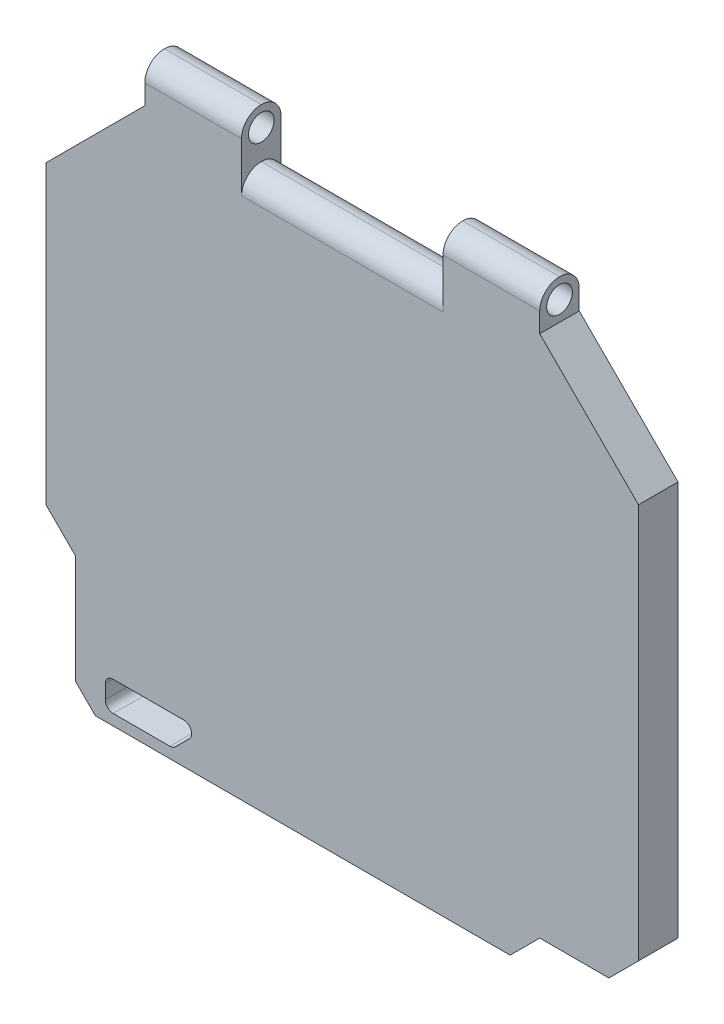
SolidWorks part; units mm, degrees
ref_plane "前视基准面" through (0, 0, 0) normal (0, 0, 1) x (1, 0, 0)
ref_plane "上视基准面" through (0, 0, 0) normal (0, 1, 0) x (1, 0, 0)
ref_plane "右视基准面" through (0, 0, 0) normal (1, 0, 0) x (0, 0, -1)
sketch "草图1" plane through (0, 0, 0) normal (0, 0, 1) x (1, 0, 0)
  line L1 (-15, -15) -> (15, -15)
  line L2 (-15, -15) -> (-15, 15)
  line L3 (-15, 15) -> (15, 15)
  line L4 (15, -15) -> (15, 15)
  line L5 (-15, -15) -> (15, 15) construction
  line L6 (-15, 15) -> (15, -15) construction
  point P0 (0, 0)
  dimension "D1" = 30
  dimension "D2" = 30
extrude "凸台-拉伸1" add sketch "草图1" along normal blind 2
sketch "草图2" plane through (0, 15, 0) normal (0, 1, 0) x (1, 0, 0)
  line L0 (15, 0) -> (-15, 0) construction
  line L1 (-5.1, -2) -> (5.1, -2)
  line L2 (-5.1, -2) -> (-5.1, 0)
  line L3 (-5.1, 0) -> (5.1, 0)
  line L4 (5.1, -2) -> (5.1, 0)
  line L5 (-5.1, -2) -> (5.1, 0) construction
  line L6 (-5.1, 0) -> (5.1, -2) construction
  line L7 (15, -2) -> (-15, -2) construction
  point P0 (0, -1)
  point P7 (0, -2)
  dimension "D1" = 10.2
extrude "切除-拉伸1" cut sketch "草图2" against normal blind 2.5
sketch "草图4" plane through (0, 0, 0) normal (0, 0, -1) x (-1, 0, 0)
  line L0 (-10, -13.5) -> (-8.5, -15)
  line L1 (-15, -15) -> (-10, -15)
  line L2 (-15, -15) -> (-15, -13.5)
  line L3 (-15, -13.5) -> (-10, -13.5)
  line L5 (15, -15) -> (-15, -15) construction
  line L6 (-8.5, -15) -> (-10, -15)
  dimension "D1" = 5
  dimension "D2" = 1.5
  dimension "D3" = 1.5
  dimension "D4" = 45
extrude "切除-拉伸3" cut sketch "草图4" against normal blind 43
chamfer "倒角1" distance 1.5 angle 45 1 edges at (15, -13.5, 1)
sketch "草图5" plane through (0, 0, 0) normal (0, 0, -1) x (-1, 0, 0)
  line L0 (-15, -12) -> (-5, -12)
  line L1 (-5, -12) -> (-2, -15)
  line L2 (-8.5, -15) -> (-2, -15)
  line L3 (15, -15) -> (-8.5, -15) construction
  line L14 (-15, 15) -> (-15, -12)
  line L15 (-15, -12) -> (-13.5, -13.5)
  line L16 (-13.5, -13.5) -> (-10, -13.5)
  line L17 (-10, -13.5) -> (-8.5, -15)
  line L18 (-8.5, -15) -> (15, -15)
  line L20 (15, -15) -> (15, 15)
  line L22 (15, 15) -> (5.1, 15)
  line L23 (5.1, 15) -> (5.1, 12.5)
  line L24 (5.1, 12.5) -> (-5.1, 12.5)
  line L25 (-5.1, 12.5) -> (-5.1, 15)
  line L26 (-5.1, 15) -> (-15, 15)
  line L29 (-15, -12) -> (-13.5, -13.5)
  line L30 (-13.5, -13.5) -> (-10, -13.5)
  line L31 (-10, -13.5) -> (-8.5, -15)
  dimension "D2" = 45
  dimension "D3" = 10
  dimension "D1" = 0
extrude "切除-拉伸4" cut sketch "草图5" against normal blind 0.5
fillet "圆角1" radius 1 6 edges at (10.05, 15, 2) (10.05, 15, 0) (-10.05, 15, 2) (-10.05, 15, 0) (0, 12.5, 2) (0, 12.5, 0)
sketch "草图3" plane through (-5.1, 0, 0) normal (1, 0, 0) x (0, 0, -1)
  circle A0 centre (-1, 14) radius 0.65
  arc A1 (0, 14) -> (-1, 15) centre (-1, 14) ccw construction
  dimension "D1" = 1.3
extrude "切除-拉伸2" cut sketch "草图3" against normal blind 43 and the other way blind 43
sketch "草图9" plane through (0, 0, 0) normal (0, 0, -1) x (-1, 0, 0)
  line L0 (-2.2933, -12.5854) -> (-0.408, -14.4707)
  line L1 (-0.3373, -14.5) -> (1.5006, -14.5)
  line L2 (1.536, -14.4146) -> (-0.3494, -12.5293)
  line L3 (-0.4201, -12.5) -> (-2.258, -12.5)
  line L4 (15, -15) -> (-2, -15) construction
  line L5 (-5, -12) -> (-15, -12) construction
  line L6 (-2, -15) -> (-5, -12) construction
  line L7 (2.5799, -12.5) -> (0.742, -12.5)
  line L8 (0.7067, -12.5854) -> (2.592, -14.4707)
  line L9 (2.6627, -14.5) -> (4.5006, -14.5)
  line L10 (4.536, -14.4146) -> (2.6506, -12.5293)
  line L11 (5.5799, -12.5) -> (3.742, -12.5)
  line L12 (3.7067, -12.5854) -> (5.592, -14.4707)
  line L13 (5.6627, -14.5) -> (7.5006, -14.5)
  line L14 (7.536, -14.4146) -> (5.6506, -12.5293)
  arc A0 (1.5006, -14.5) -> (1.536, -14.4146) centre (1.5006, -14.45) ccw
  arc A1 (-2.2933, -12.5854) -> (-2.258, -12.5) centre (-2.258, -12.55) cw
  arc A2 (-0.3373, -14.5) -> (-0.408, -14.4707) centre (-0.3373, -14.4) cw
  arc A3 (-0.3494, -12.5293) -> (-0.4201, -12.5) centre (-0.4201, -12.6) ccw
  arc A4 (2.6506, -12.5293) -> (2.5799, -12.5) centre (2.5799, -12.6) ccw
  arc A5 (0.7067, -12.5854) -> (0.742, -12.5) centre (0.742, -12.55) cw
  arc A6 (2.6627, -14.5) -> (2.592, -14.4707) centre (2.6627, -14.4) cw
  arc A7 (4.5006, -14.5) -> (4.536, -14.4146) centre (4.5006, -14.45) ccw
  arc A8 (5.6506, -12.5293) -> (5.5799, -12.5) centre (5.5799, -12.6) ccw
  arc A9 (3.7067, -12.5854) -> (3.742, -12.5) centre (3.742, -12.55) cw
  arc A10 (5.6627, -14.5) -> (5.592, -14.4707) centre (5.6627, -14.4) cw
  arc A11 (7.5006, -14.5) -> (7.536, -14.4146) centre (7.5006, -14.45) ccw
  point P9 (-2.3787, -12.5)
  point P14 (-0.3787, -12.5)
  dimension "D4" = 0.05
  dimension "D5" = 0.1
  dimension "D1" = 3
  dimension "D2" = 2
  dimension "D3" = 0.5
  dimension "D6" = 0.5
  dimension "D7" = 1.5
extrude "切除-拉伸7" cut sketch "草图9" against normal blind 0.5
sketch "草图10" plane through (0, 0, 0) normal (0, 0, -1) x (-1, 0, 0)
  line L0 (8.027, -12.95) -> (11.6, -12.95)
  line L2 (8.4441, -14.3328) -> (7.7441, -13.6328)
  line L3 (8.727, -14.45) -> (11.6, -14.45)
  line L4 (12, -14.05) -> (12, -13.35)
  line L5 (7.536, -14.4146) -> (5.6506, -12.5293) construction
  arc A7 (8.727, -14.45) -> (8.4441, -14.3328) centre (8.727, -14.05) cw
  arc A8 (12, -14.05) -> (11.6, -14.45) centre (11.6, -14.05) cw
  arc A9 (11.6, -12.95) -> (12, -13.35) centre (11.6, -13.35) cw
  arc A12 (7.7441, -13.6328) -> (8.027, -12.95) centre (8.027, -13.35) cw
  point P2 (7.4648, -13.3536)
  point P3 (7.1595, -12.95)
  point P7 (7.4648, -13.3536)
  point P8 (7.3184, -13)
  point P15 (7.5101, -13.3514)
  point P19 (7.0563, -12.95)
  point P20 (6.9408, -12.945)
  point P21 (-8.5, -15)
  point P22 (6.9686, -12.8573)
  dimension "D3" = 0.4
  dimension "D4" = 1.5
  dimension "D1" = 20.5
  dimension "D2" = 0.7
extrude "切除-拉伸8" cut sketch "草图10" against normal blind 10
sketch "草图11" plane through (0, 0, 0) normal (0, 0, -1) x (-1, 0, 0)
  line L0 (15, 14) -> (15, -15) construction
  line L1 (15, -7) -> (13.5, -8.5)
  line L2 (15, -7) -> (15, -15)
  line L3 (15, -15) -> (13.5, -15)
  line L4 (13.5, -8.5) -> (13.5, -15)
  line L5 (15, -15) -> (-2, -15) construction
  dimension "D1" = 1.5
  dimension "D2" = 135
  dimension "D3" = 8
extrude "切除-拉伸9" cut sketch "草图11" against normal blind 10
chamfer "倒角2" distance 1 angle 45 1 edges at (-13.5, -15, 1)
sketch "草图12" plane through (0, 0, 0) normal (0, 0, -1) x (-1, 0, 0)
  line L0 (10, 15) -> (10, 13)
  line L3 (15, 14) -> (15, -7) construction
  line L4 (15, 8) -> (15, 15)
  line L5 (15, 15) -> (10, 15)
  line L8 (13, 10) -> (15, 8)
  line L9 (10, 13) -> (13, 10)
  dimension "D1" = 45
  dimension "D2" = 5
  dimension "D3" = 2
extrude "切除-拉伸10" cut sketch "草图12" against normal blind 10
ref_plane "基准面2" through (0, 0, 0) normal (1, 0, 0) x (0, 0, -1)
mirror "镜向4" about plane through (0, 0, 0) normal (1, 0, 0) of "切除-拉伸10"
